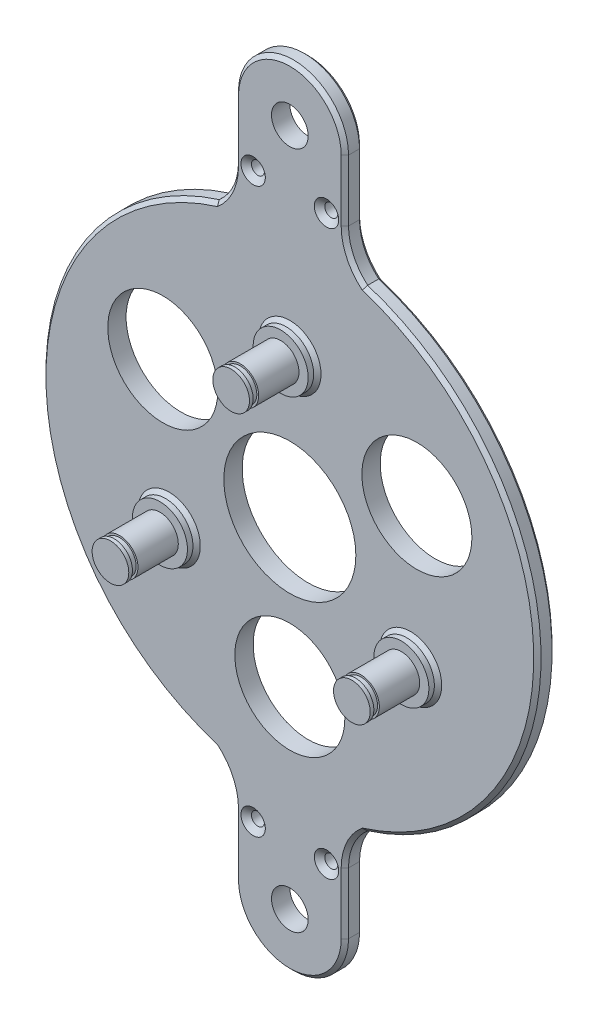
SolidWorks part; units mm, degrees
material "PET"
ref_plane "Front Plane" through (0, 0, 0) normal (0, 0, 1) x (1, 0, 0)
ref_plane "Top Plane" through (0, 0, 0) normal (0, 1, 0) x (1, 0, 0)
ref_plane "Right Plane" through (0, 0, 0) normal (1, 0, 0) x (0, 0, -1)
ref_axis "X AXIS" through (-94.2975, 0, 0) along (1, 0, 0)
ref_axis "Y AXIS" through (0, 147.6375, 0) along (0, -1, 0)
ref_axis "Z AXIS" through (0, 0, -1.3335) along (0, 0, 1)
sketch "Sketch1" plane through (0, 0, 0) normal (0, 0, 1) x (1, 0, 0)
  line L0 (0, 147.6375) -> (0, -96.8375) construction
  line L1 (0, 0) -> (41.7944, -24.13) construction
  line L2 (0, 0) -> (-41.7944, -24.13) construction
  line L3 (0, 0) -> (0, 48.26) construction
  circle A0 centre (0, 0) radius 15.875 construction
  circle A1 centre (0, 48.26) radius 32.385 construction
  circle A2 centre (41.7944, -24.13) radius 32.385 construction
  circle A3 centre (-41.7944, -24.13) radius 32.385 construction
  circle A4 centre (0, 0) radius 85.725
  point P14 (0, 0)
  dimension "D1" = 31.75
  dimension "D2" = 64.77
  dimension "D5" = 171.45
  dimension "D4" = 120
  dimension "D3" = 3
extrude "Boss-Extrude1" add sketch "Sketch1" along normal blind 6.35
sketch "Sketch2" plane through (0, 0, 0) normal (0, 0, 1) x (1, 0, 0)
  circle A0 centre (41.7944, -24.13) radius 6.35
  circle A1 centre (0, 48.26) radius 6.35
  circle A2 centre (-41.7944, -24.13) radius 6.35
  dimension ".500" = 12.7
extrude "Boss-Extrude2" add sketch "Sketch2" along normal blind 26.67
sketch "Sketch6" plane through (0, 0, 0) normal (0, 0, 1) x (1, 0, 0)
  circle A0 centre (0, 0) radius 22.86
  dimension "1.8" = 45.72
extrude "Cut-Extrude1" cut sketch "Sketch6" along direction (0, 0, 1) on the side of the normal up to next (6.35 mm away)
sketch "Sketch7" plane through (0, 0, 26.67) normal (0, 0, 1) x (1, 0, 0)
  circle A0 centre (0, 48.26) radius 4.7625
  dimension "D1" = 9.525
sketch "Sketch10" plane through (0, 0, 0) normal (0, 0, 1) x (1, 0, 0)
  line L0 (0, 0) -> (74.24, 42.8625) construction
  line L1 (0, 0) -> (41.7944, -24.13) construction
  circle A0 centre (0, 0) radius 85.725 construction
  circle A1 centre (43.9941, 25.4) radius 19.05
  dimension "D3" = 38.1
  dimension "D1" = 60
  dimension "D2" = 50.8
extrude "Cut-Extrude3" cut sketch "Sketch10" along normal up to next
sketch "Sketch11" plane through (0, 0, 0) normal (0, 0, 1) x (1, 0, 0)
  circle A0 centre (0, 48.26) radius 9.525
  dimension "D1" = 19.05
extrude "Boss-Extrude3" add sketch "Sketch11" along normal blind 9.525
sketch "Sketch12" plane through (0, 0, 0) normal (1, 0, 0) x (0, 0, -1)
  line L0 (-26.67, 48.26) -> (-36.8537, 48.26) construction
  line L1 (-26.67, 53.0225) -> (-26.67, 43.4975) construction
  line L2 (-9.525, 54.61) -> (-26.67, 54.61) construction
  line L3 (-9.525, 54.61) -> (-26.67, 54.61) construction
  line L5 (-25.4, 53.975) -> (-23.495, 53.975)
  line L6 (-25.4, 53.975) -> (-25.4, 55.245)
  line L7 (-25.4, 55.245) -> (-23.495, 55.245)
  line L8 (-23.495, 53.975) -> (-23.495, 55.245)
  line L9 (-25.4, 53.975) -> (-23.495, 55.245) construction
  line L10 (-25.4, 55.245) -> (-23.495, 53.975) construction
  point P6 (-24.4475, 54.61)
  dimension "D1" = 13.97
  dimension "D2" = 1.905
  dimension "D3" = 11.43
revolve "Cut-Revolve1" cut sketch "Sketch12" angle 360 about L0
pattern_circular "CirPattern6" count 3 over 360 about axis through (0, 0, 6.35) along (0, 0, 1) of "Boss-Extrude3"
pattern_circular "CirPattern7" count 3 over 360 about axis through (0, 0, 6.35) along (0, 0, 1) of "Cut-Revolve1"
chamfer "Chamfer2" distance 1.27 angle 45 5 edges at (85.725, 0, 6.35) (85.725, 0, 0) (-32.2694, -24.13, 6.35) (51.3194, -24.13, 6.35) (9.525, 48.26, 6.35)
sketch "Sketch13" plane through (0, 0, 0) normal (0, 0, 1) x (1, 0, 0)
  line L0 (0, 0.0201) -> (0, 136.5451) construction
  line L2 (-19.05, 82.2785) -> (19.05, 82.2785)
  line L3 (-19.05, 82.2785) -> (-19.05, 136.5451)
  line L4 (-19.05, 136.5451) -> (19.05, 136.5451)
  line L5 (19.05, 82.2785) -> (19.05, 136.5451)
  line L6 (-19.05, 82.2785) -> (19.05, 136.5451) construction
  line L7 (-19.05, 136.5451) -> (19.05, 82.2785) construction
  circle A0 centre (0, 0.0201) radius 88.9 construction
  circle A4 centre (0, 0) radius 84.455 construction
  dimension "D1" = 177.8
  dimension "D2" = 136.525
  dimension "D3" = 38.1
  dimension "D4" = 54.2667
  dimension "D5" = 82.2583
extrude "Boss-Extrude5" add sketch "Sketch13" along a picked direction on the side of the normal blind 6.35
pattern_circular "CirPattern8" count 3 over 360 about axis through (0, 0, 6.35) along (0, 0, 1) of "Cut-Extrude3" reverse direction yes
sketch "Sketch14" plane through (0, 0, 0) normal (0, 0, 1) x (1, 0, 0)
  line L0 (0, 22.86) -> (0, 136.5451) construction
  line L1 (19.05, 136.5451) -> (-19.05, 136.5451) construction
  circle A0 centre (0, 0) radius 22.86 construction
  circle A1 centre (0, 117.4951) radius 6.35
  dimension "D2" = 12.7
  dimension "D1" = 19.05
fillet "Fillet1" 2 edges at (-19.05, 136.5451, 3.175) (19.05, 136.5451, 3.175) type full round first side face at (-19.05, 100.8017, 3.3867) second side face at (19.05, 100.8017, 2.9633) middle face at (0, 136.5451, 3.175)
sketch "Sketch25" plane through (0, 0, 0) normal (0, 0, 1) x (1, 0, 0)
  line L1 (-19.05, 117.4951) -> (-19.05, 82.2785) construction
  line L3 (-19.05, 96.2376) -> (-19.05, 82.2785)
  arc A1 (-31.0877, 78.5252) -> (-19.05, 96.2376) centre (-38.1, 96.2376) ccw
  arc A4 (-19.05, 82.2785) -> (19.05, 82.2785) centre (0, 0) ccw construction
  arc A5 (-19.05, 82.2785) -> (-31.0877, 78.5252) centre (0, 0) ccw
  dimension "D1" = 38.1
  dimension "D2" = 84.455
extrude "Boss-Extrude9" add sketch "Sketch25" along normal blind 6.35
mirror "Mirror1" about plane through (0, 0, 0) normal (1, 0, 0) of "Boss-Extrude9"
sketch "Sketch26" plane through (0, 0, 0) normal (0, 0, 1) x (1, 0, 0)
  line L0 (0, 0) -> (0, 136.5451) construction
  line L1 (0, 0) -> (-12.7, 97.6022) construction
  line L2 (0, 0) -> (12.7, 97.6022) construction
  circle A0 centre (0, 0) radius 90.4875 construction
  circle A1 centre (0, 0) radius 98.425 construction
  arc A2 (19.05, 117.4951) -> (-19.05, 117.4951) centre (0, 117.4951) ccw construction
  circle A3 centre (-12.7, 97.6022) radius 2.3812
  circle A4 centre (12.7, 97.6022) radius 2.3812
  dimension "D1" = 180.975
  dimension "D2" = 196.85
  dimension "D3" = 4.7625
  dimension "D6" = 4.7625
  dimension "D4" = 12.7
  dimension "D5" = 12.7
hole_wizard "CSK for #8 Flat Head Machine Screw (100)2" positions "Sketch31" profile "Sketch32" countersink size "#8" standard "ANSI Inch" end condition through all
sketch "Sketch31" plane through (0, 0, 6.35) normal (0, 0, 1) x (1, 0, 0)
  point P0 (-12.7, 97.6022)
  point P3 (12.7, 97.6022)
sketch "Sketch32" plane through (-12.7, 97.6022, 6.35) normal (1, 0, 0) x (0, -1, 0)
  line L0 (0, 0) -> (0, 6.35)
  line L1 (0, 6.35) -> (2.2479, 6.35)
  line L2 (2.2479, 6.35) -> (2.2479, 1.6518)
  line L3 (2.2479, 1.6518) -> (4.2164, 0)
  line L5 (4.2164, 0) -> (0, 0)
  line L6 (-2.2479, 1.6518) -> (-4.2164, 0) construction
  line L11 (0, -6.35) -> (0, 107.95) construction
  dimension "Thru Hole Dia." = 4.4958
  dimension "Thru Hole Depth" = 6.35
  dimension "Near C'Sink Dia." = 8.4328
  dimension "Near C'Sink Angle" = 100
hole_wizard "1/2 (0.5) Diameter Hole2" positions "Sketch33" profile "Sketch34" hole size "1/2" standard "ANSI Inch" end condition through all
sketch "Sketch33" plane through (0, 0, 6.35) normal (0, 0, 1) x (1, 0, 0)
  point P0 (0, 117.4951)
sketch "Sketch34" plane through (0, 117.4951, 6.35) normal (1, 0, 0) x (0, -1, 0)
  line L0 (0, 0) -> (0, 6.35)
  line L1 (0, 6.35) -> (6.35, 6.35)
  line L2 (6.35, 6.35) -> (6.35, 0)
  line L5 (6.35, 0) -> (0, 0)
  line L11 (0, -6.35) -> (0, 107.95) construction
  dimension "Thru Hole Dia." = 12.7
  dimension "Thru Hole Depth" = 6.35
mirror "Mirror3" about plane through (0, 0, 0) normal (0, 1, 0) of "1/2 (0.5) Diameter Hole2", "CSK for #8 Flat Head Machine Screw (100)2", "Mirror1", "Boss-Extrude9", "Fillet1", "Boss-Extrude5"
chamfer "Chamfer3" distance 1.27 angle 45 16 edges at (22.3443, -85.5297, 0) (19.05, -106.8664, 0) (0, -136.5451, 0) (22.3443, -85.5297, 6.35) (19.05, -106.8664, 6.35) (0, -136.5451, 6.35) (-22.3443, 85.5297, 0) (22.3443, 85.5297, 0) (-19.05, 106.8664, 0) (19.05, 106.8664, 0) (0, 136.5451, 0) (22.3443, 85.5297, 6.35) (19.05, 106.8664, 6.35) (0, 136.5451, 6.35) (-19.05, 106.8664, 6.35) (-22.3443, 85.5297, 6.35)
